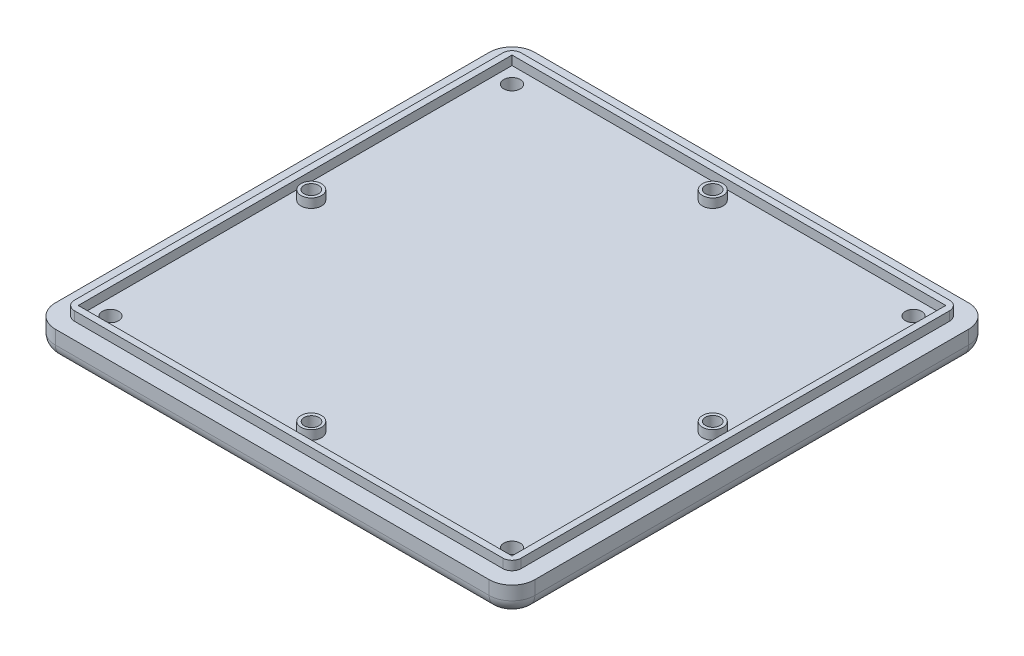
SolidWorks part; units mm, degrees
ref_plane "Front Plane" through (0, 0, 0) normal (0, 0, 1) x (1, 0, 0)
ref_plane "Top Plane" through (0, 0, 0) normal (0, 1, 0) x (1, 0, 0)
ref_plane "Right Plane" through (0, 0, 0) normal (1, 0, 0) x (0, 0, -1)
sketch "Sketch1" plane through (0, 0, 0) normal (0, 1, 0) x (1, 0, 0)
  line L0 (0, 105) -> (105, 0) construction
  line L1 (5, 0) -> (100, 0)
  line L2 (0, 5) -> (0, 100)
  line L3 (5, 105) -> (100, 105)
  line L4 (105, 5) -> (105, 100)
  line L5 (0, 0) -> (105, 105) construction
  arc A0 (100, 0) -> (105, 5) centre (100, 5) ccw
  arc A1 (0, 100) -> (5, 105) centre (5, 100) cw
  arc A2 (100, 105) -> (105, 100) centre (100, 100) cw
  arc A3 (5, 0) -> (0, 5) centre (5, 5) cw
  dimension "D3" = 5
  dimension "D1" = 105
  dimension "D2" = 105
extrude "Boss-Extrude1" add sketch "Sketch1" along normal blind 6
fillet "Fillet1" radius 3 8 edges at (1.4645, 0, -103.5355) (52.5, 0, -105) (103.5355, 0, -103.5355) (105, 0, -52.5) (103.5355, 0, -1.4645) (1.4645, 0, -1.4645) (0, 0, -52.5) (52.5, 0, 0)
sketch "Sketch2" plane through (0, 0, 0) normal (0, -1, 0) x (1, 0, 0)
  line L0 (100, -5) -> (96.4645, -8.5355) construction
  line L1 (100, -100) -> (96.4645, -96.4645) construction
  line L2 (5, -5) -> (8.5355, -8.5355) construction
  line L3 (5, -100) -> (8.5355, -96.4645) construction
  point P12 (0, 0)
  dimension "D1" = 5
  dimension "D2" = 5
  dimension "D3" = 5
  dimension "D4" = 5
hole_wizard "CSK for M3 Flat Head Machine Screw1" positions "3DSketch1" profile "Sketch4" countersink size "M3" standard "ANSI Metric" end condition through all
sketch3d "3DSketch1"
  point P0 (8.5355, 0, -8.5355)
  point P3 (8.5355, 0, -96.4645)
  point P6 (96.4645, 0, -96.4645)
  point P9 (96.4645, 0, -8.5355)
sketch "Sketch4" plane through (8.5355, 0, -8.5355) normal (1, 0, 0) x (0, 0, -1)
  line L0 (0, 0) -> (0, 6)
  line L1 (0, 6) -> (1.8, 6)
  line L2 (1.8, 6) -> (1.8, 1.35)
  line L3 (1.8, 1.35) -> (3.15, 0)
  line L5 (3.15, 0) -> (0, 0)
  line L6 (-1.8, 1.35) -> (-3.15, 0) construction
  line L11 (0, -6.35) -> (0, 107.95) construction
  dimension "Thru Hole Dia." = 3.6
  dimension "Thru Hole Depth" = 6
  dimension "Near C'Sink Dia." = 6.3
  dimension "Near C'Sink Angle" = 90
sketch "Sketch5" plane through (0, 6, 0) normal (0, 1, 0) x (1, 0, 0)
  line L0 (100, 100) -> (101.4142, 101.4142) construction
  line L1 (7, 5) -> (98, 5)
  line L2 (5, 7) -> (5, 98)
  line L3 (7, 100) -> (98, 100)
  line L4 (100, 7) -> (100, 98)
  line L5 (100, 100) -> (5, 100)
  line L6 (100, 100) -> (100, 5)
  line L7 (100, 5) -> (5, 5)
  line L8 (5, 100) -> (5, 5)
  line L9 (5, 100) -> (3.5858, 101.4142) construction
  line L10 (5, 5) -> (3.5858, 3.5858)
  line L11 (100, 5) -> (101.4142, 3.5858) construction
  line L13 (5.5858, 3.5858) -> (99.4142, 3.5858)
  line L14 (3.5858, 5.5858) -> (3.5858, 99.4142)
  line L15 (5.5858, 101.4142) -> (99.4142, 101.4142)
  line L16 (101.4142, 5.5858) -> (101.4142, 99.4142)
  arc A0 (98, 5) -> (100, 7) centre (98, 7) ccw
  arc A1 (7, 5) -> (5, 7) centre (7, 7) cw
  arc A2 (5, 98) -> (7, 100) centre (7, 98) cw
  arc A3 (98, 100) -> (100, 98) centre (98, 98) cw
  arc A4 (101.4142, 5.5858) -> (99.4142, 3.5858) centre (99.4142, 5.5858) cw
  arc A5 (3.5858, 5.5858) -> (5.5858, 3.5858) centre (5.5858, 5.5858) ccw
  arc A6 (5.5858, 101.4142) -> (3.5858, 99.4142) centre (5.5858, 99.4142) ccw
  arc A7 (101.4142, 99.4142) -> (99.4142, 101.4142) centre (99.4142, 99.4142) ccw
  point P11 (5, 5)
  point P16 (100, 100)
  dimension "D1" = 2
  dimension "D6" = 2
  dimension "D2" = 2
  dimension "D3" = 2
  dimension "D4" = 2
  dimension "D5" = 2
extrude "Boss-Extrude2" add sketch "Sketch5" along normal blind 2 contours L16 A7 L15 A6 L14 A5 L8 L2 L5 L3 L6 L4 L7 L1 L13 A4 region at (3.8658, 6, -4.8734)
sketch "Sketch6" plane through (0, 6, 0) normal (0, 1, 0) x (1, 0, 0)
  line L0 (96.4645, 8.5355) -> (96.4645, 96.4645) construction
  line L1 (8.5355, 8.5355) -> (96.4645, 8.5355) construction
  line L2 (8.5355, 8.5355) -> (8.5355, 96.4645) construction
  line L3 (8.5355, 96.4645) -> (96.4645, 96.4645) construction
  circle A0 centre (8.5355, 52.5) radius 2.25
  circle A1 centre (52.5, 8.5355) radius 2.25
  circle A2 centre (96.4645, 52.5) radius 2.25
  circle A3 centre (52.5, 96.4645) radius 2.25
  dimension "D1" = 4.5
  dimension "D2" = 4.5
  dimension "D3" = 4.5
  dimension "D4" = 4.5
extrude "Boss-Extrude3" add sketch "Sketch6" along normal blind 2
hole_wizard "M3 Clearance Hole1" positions "3DSketch2" profile "Sketch8" hole size "M3" standard "ANSI Metric"
sketch3d "3DSketch2"
  line L0 (8.5355, 8, -52.5) -> (8.5355, 6, -52.5) construction
  line L1 (96.4645, 8, -52.5) -> (96.4645, 6, -52.5) construction
  line L2 (52.5, 8, -96.4645) -> (52.5, 6, -96.4645) construction
  point P0 (8.5355, 8, -52.5)
  point P4 (52.5797, 8, -8.5164)
  point P6 (96.4645, 8, -52.5)
  point P10 (52.5, 8, -96.4645)
sketch "Sketch8" plane through (8.5355, 8, -52.5) normal (1, 0, 0) x (0, 0, 1)
  line L0 (0, 0) -> (0, 5.9614)
  line L1 (0, 5.9614) -> (1.6, 5)
  line L2 (1.6, 5) -> (1.6, 0)
  line L5 (1.6, 0) -> (0, 0)
  line L10 (0, 5.9614) -> (-1.6, 5) construction
  line L11 (0, -6.35) -> (0, 107.95) construction
  dimension "Hole Dia." = 3.2
  dimension "Hole Depth" = 5
  dimension "Drill Angle" = 118
